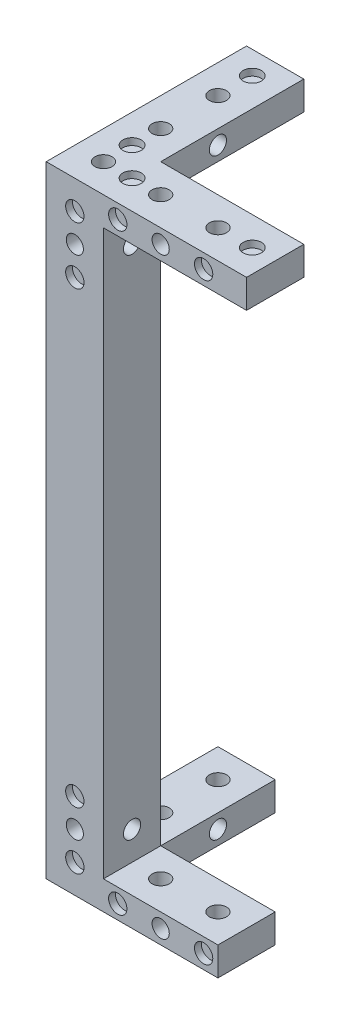
SolidWorks part; units mm, degrees
ref_plane "Front Plane" through (0, 0, 0) normal (0, 0, 1) x (1, 0, 0)
ref_plane "Top Plane" through (0, 0, 0) normal (0, 1, 0) x (1, 0, 0)
ref_plane "Right Plane" through (0, 0, 0) normal (1, 0, 0) x (0, 0, -1)
sketch "Sketch1" plane through (0, 0, 0) normal (0, 1, 0) x (1, 0, 0)
  line L1 (0, 0) -> (30, 0)
  line L2 (0, 0) -> (0, 10)
  line L3 (0, 10) -> (30, 10)
  line L4 (30, 0) -> (30, 10)
  line L5 (0, 0) -> (10, 0)
  line L6 (0, 0) -> (0, 30)
  line L7 (0, 30) -> (10, 30)
  line L8 (10, 0) -> (10, 30)
  dimension "D1" = 10
  dimension "D2" = 10
  dimension "D3" = 30
  dimension "D4" = 30
extrude "Boss-Extrude1" add sketch "Sketch1" along normal blind 10 contours L3 L8 L7 L6 | L1 L8 L3 L2 | L8 L1 L4 L3 region at (5, 0, -5) region at (20, 0, -5) region at (5, 0, -20)
sketch "Sketch2" plane through (0, 10, 0) normal (0, 1, 0) x (1, 0, 0)
  line L1 (0, 0) -> (10, 0)
  line L2 (0, 0) -> (0, 10)
  line L3 (0, 10) -> (10, 10)
  line L4 (10, 0) -> (10, 10)
extrude "Boss-Extrude2" add sketch "Sketch2" along normal blind 93.5
sketch "Sketch3" plane through (0, 103.5, 0) normal (0, 1, 0) x (1, 0, 0)
  line L1 (0, 0) -> (30, 0)
  line L2 (0, 0) -> (0, 10)
  line L3 (0, 10) -> (30, 10)
  line L4 (30, 0) -> (30, 10)
  line L5 (0, 0) -> (10, 0)
  line L6 (0, 0) -> (0, 30)
  line L7 (0, 30) -> (10, 30)
  line L8 (10, 0) -> (10, 30)
  line M9 (0, 10) -> (0, 0)
  line M10 (0, 0) -> (10, 0)
  line M11 (10, 0) -> (10, 10)
  line M12 (10, 10) -> (0, 10)
  dimension "D1" = 10
  dimension "D2" = 30
  dimension "D3" = 10
  dimension "D4" = 30
extrude "Boss-Extrude3" add sketch "Sketch3" along normal blind 5 contours L8 L7 L6 M12 | M12 M9 M10 M11 | L1 L4 L3 M11 region at (5, 103.5, -5) region at (20, 103.5, -5) region at (5, 103.5, -20)
sketch "Sketch4" plane through (0, 10, 0) normal (0, 1, 0) x (1, 0, 0)
  line L1 (30, 10) -> (10, 10)
  line L2 (30, 10) -> (30, 0)
  line L3 (30, 0) -> (10, 0)
  line L4 (10, 10) -> (10, 0)
  line L5 (10, 30) -> (0, 30)
  line L6 (10, 30) -> (10, 10)
  line L7 (10, 10) -> (0, 10)
  line L8 (0, 30) -> (0, 10)
  line M1 (10, 10) -> (10, 0)
  line M2 (10, 0) -> (30, 0)
  line M3 (30, 0) -> (30, 10)
  line M4 (30, 10) -> (10, 10)
extrude "Cut-Extrude1" cut sketch "Sketch4" against normal blind 5 contours L5 L8 L7 L6 | M4 M1 M2 M3 region at (20, 10, -5) region at (5, 10, -20)
sketch "Sketch5" plane through (0, 0, 0) normal (0, 0, 1) x (1, 0, 0)
  line L0 (10, 103.5) -> (10, 5) construction
  line L1 (0, 0) -> (30, 0) construction
  line L2 (10, 5) -> (30, 5) construction
  line L3 (30, 5) -> (30, 0) construction
  line L4 (0, 108.5) -> (0, 0) construction
  line L5 (0, 108.5) -> (0, 0)
  line L6 (0, 54.25) -> (10, 54.25)
  circle A0 centre (5, 5) radius 1.6
  circle A1 centre (27.5, 2.5) radius 1.6
  circle A2 centre (5, 15) radius 1.6
  circle A3 centre (12.5, 2.5) radius 1.6
  circle A4 centre (27.5, 106) radius 1.6
  circle A5 centre (12.5, 106) radius 1.6
  circle A6 centre (5, 103.5) radius 1.6
  circle A7 centre (5, 93.5) radius 1.6
  dimension "D1" = 3.2
  dimension "D2" = 5
  dimension "D3" = 5
  dimension "D4" = 3.2
  dimension "D5" = 2.5
  dimension "D6" = 2.5
  dimension "D7" = 2.5
  dimension "D8" = 3.2
  dimension "D9" = 5
  dimension "D10" = 10
  dimension "D11" = 3.2
  dimension "D12" = 15
extrude "Cut-Extrude2" cut sketch "Sketch5" against normal blind 1.2 contours A4 | A5 | A6 | A7 | A2 | A0 | A3 | A1
sketch "Sketch6" plane through (0, 0, 0) normal (0, 0, 1) x (1, 0, 0)
  line L0 (10, 103.5) -> (30, 103.5) construction
  line L1 (10, 103.5) -> (10, 5) construction
  line L2 (0, 108.5) -> (0, 0)
  line L3 (0, 54.25) -> (10, 54.25)
  circle A0 centre (5, 98.5) radius 1.5
  circle A1 centre (20, 106) radius 1.5
  circle A2 centre (5, 103.5) radius 1.6 construction
  circle A4 centre (20, 2.5) radius 1.5
  circle A5 centre (5, 10) radius 1.5
  circle A6 centre (27.5, 106) radius 1.6 construction
  circle A7 centre (12.5, 106) radius 1.6 construction
  dimension "D1" = 3
  dimension "D2" = 2.5
  dimension "D3" = 5
  dimension "D4" = 3
  dimension "D5" = 5
  dimension "D6" = 7.5
  dimension "D7" = 7.5
extrude "Cut-Extrude3" cut sketch "Sketch6" against normal blind 10 contours A1 | A0 | A5 | A4 region at (5, 98.5, 0) region at (20, 106, 0) region at (20, 2.5, 0) region at (5, 10, 0)
sketch "Sketch7" plane through (0, 0, 0) normal (-1, 0, 0) x (0, 0, 1)
  line L0 (0, 108.5) -> (-30, 108.5) construction
  line L1 (0, 108.5) -> (0, 0) construction
  line L5 (-30, 108.5) -> (-30, 103.5) construction
  line L8 (0, 108.5) -> (0, 0)
  line L9 (0, 54.25) -> (-10, 54.25)
  line L10 (-10, 103.5) -> (-10, 5) construction
  circle A0 centre (-27.5, 106) radius 1.6
  circle A1 centre (-12.5, 106) radius 1.6
  circle A2 centre (-5, 103.5) radius 1.6
  circle A3 centre (-5, 93.5) radius 1.6
  circle A4 centre (-5, 15) radius 1.6
  circle A5 centre (-5, 5) radius 1.6
  circle A6 centre (-12.5, 2.5) radius 1.6
  circle A7 centre (-27.5, 2.5) radius 1.6
  dimension "D1" = 3.2
  dimension "D2" = 3.2
  dimension "D3" = 3.2
  dimension "D4" = 3.2
  dimension "D5" = 2.5
  dimension "D6" = 2.5
  dimension "D7" = 5
  dimension "D8" = 5
  dimension "D9" = 2.5
  dimension "D10" = 15
  dimension "D11" = 5
  dimension "D12" = 10
extrude "Cut-Extrude4" cut sketch "Sketch7" against normal blind 1.2 contours A0 | A1 | A2 | A3 | A7 | A6 | A5 | A4 region at (0, 106, -27.5) region at (0, 106, -12.5) region at (0, 103.5, -5) region at (0, 93.5, -5) region at (0, 15, -5) region at (0, 5, -5) region at (0, 2.5, -12.5) region at (0, 2.5, -27.5)
sketch "Sketch8" plane through (0, 0, 0) normal (-1, 0, 0) x (0, 0, 1)
  line L0 (0, 108.5) -> (-30, 108.5) construction
  line L1 (0, 108.5) -> (0, 0) construction
  line L2 (-30, 108.5) -> (-30, 103.5) construction
  line L3 (0, 108.5) -> (0, 0)
  line L4 (0, 54.25) -> (-10, 54.25)
  line L5 (-10, 103.5) -> (-10, 5) construction
  circle A0 centre (-20, 106) radius 1.5
  circle A1 centre (-5, 98.5) radius 1.5
  circle A2 centre (-5, 103.5) radius 1.6 construction
  circle A3 centre (-5, 10) radius 1.5
  circle A4 centre (-20, 2.5) radius 1.5
  dimension "D1" = 3
  dimension "D2" = 3
  dimension "D3" = 2.5
  dimension "D4" = 5
  dimension "D5" = 5
  dimension "D6" = 10
extrude "Cut-Extrude5" cut sketch "Sketch8" against normal blind 10.2 contours A4 | A3 | A0 | A1
sketch "Sketch9" plane through (0, 5, 0) normal (0, 1, 0) x (1, 0, 0)
  circle A0 centre (25, 5) radius 1.5 construction
  circle A1 centre (15, 5) radius 1.5 construction
  circle A2 centre (25, 5) radius 1.5
  circle A3 centre (15, 5) radius 1.5
  circle A4 centre (5, 15) radius 1.5 construction
  circle A5 centre (5, 25) radius 1.5 construction
  circle A6 centre (5, 15) radius 1.5
  circle A7 centre (5, 25) radius 1.5
extrude "Cut-Extrude6" cut sketch "Sketch9" against normal blind 10.2
sketch "Sketch10" plane through (0, 0, 0) normal (0, -1, 0) x (1, 0, 0)
  circle A0 centre (5, -5) radius 1.5 construction
  circle A1 centre (5, -5) radius 1.5
extrude "Cut-Extrude7" cut sketch "Sketch10" against normal blind 12.2
sketch "Sketch11" plane through (0, 108.5, 0) normal (0, 1, 0) x (1, 0, 0)
  circle A0 centre (5, 15) radius 1.5 construction
  circle A1 centre (5, 25) radius 1.5 construction
  circle A2 centre (15, 5) radius 1.5 construction
  circle A3 centre (25, 5) radius 1.5 construction
  circle A4 centre (5, 15) radius 1.5
  circle A5 centre (5, 25) radius 1.5
  circle A6 centre (15, 5) radius 1.5
  circle A7 centre (25, 5) radius 1.5
extrude "Cut-Extrude8" cut sketch "Sketch11" against normal blind 10
sketch "Sketch12" plane through (0, 108.5, 0) normal (0, 1, 0) x (1, 0, 0)
  circle A0 centre (5, 5) radius 1.5 construction
  circle A1 centre (5, 5) radius 1.5
extrude "Cut-Extrude9" cut sketch "Sketch12" against normal blind 12
sketch "Sketch13" plane through (0, 108.5, 0) normal (0, 1, 0) x (1, 0, 0)
  line L1 (0, 0) -> (30, 0) construction
  line L2 (0, 0) -> (0, 30) construction
  circle A1 centre (10, 5) radius 1.6
  circle A2 centre (5, 10) radius 1.6
  circle A6 centre (5, 15) radius 1.5 construction
  circle A8 centre (15, 5) radius 1.5 construction
  dimension "D2" = 3.2
  dimension "D4" = 3.2
  dimension "D7" = 5
  dimension "D8" = 5
  dimension "D10" = 5
  dimension "D11" = 5
extrude "Cut-Extrude10" cut sketch "Sketch13" against normal blind 1.2
sketch "Sketch14" plane through (0, 0, -30) normal (0, 0, -1) x (-1, 0, 0)
  line L4 (-10, 103.5) -> (0, 103.5)
  line L5 (0, 103.5) -> (0, 108.5)
  line L6 (0, 108.5) -> (-10, 108.5)
  line L7 (-10, 108.5) -> (-10, 103.5)
  line L8 (-10, 103.5) -> (0, 103.5)
  line L9 (0, 103.5) -> (0, 108.5)
  line L10 (0, 108.5) -> (-10, 108.5)
  line L11 (-10, 108.5) -> (-10, 103.5)
  dimension "D1" = 0
extrude "Boss-Extrude4" add sketch "Sketch14" along normal blind 5
sketch "Sketch15" plane through (30, 0, 0) normal (1, 0, 0) x (0, 0, -1)
  line L4 (0, 103.5) -> (10, 103.5)
  line L5 (10, 103.5) -> (10, 108.5)
  line L6 (10, 108.5) -> (0, 108.5)
  line L7 (0, 108.5) -> (0, 103.5)
  line L8 (0, 103.5) -> (10, 103.5)
  line L9 (10, 103.5) -> (10, 108.5)
  line L10 (10, 108.5) -> (0, 108.5)
  line L11 (0, 108.5) -> (0, 103.5)
  dimension "D1" = 0
extrude "Boss-Extrude5" add sketch "Sketch15" along normal blind 5
sketch "Sketch16" plane through (0, 108.5, 0) normal (0, 1, 0) x (1, 0, 0)
  line L0 (0, 0) -> (35, 0) construction
  line L1 (0, 0) -> (0, 35) construction
  line L2 (35, 10) -> (35, 0) construction
  line L3 (0, 35) -> (10, 35) construction
  circle A0 centre (31, 5) radius 1.6
  circle A1 centre (5, 31) radius 1.6
  dimension "D1" = 3.2
  dimension "D2" = 3.2
  dimension "D3" = 5
  dimension "D4" = 5
  dimension "D5" = 4
  dimension "D6" = 4
extrude "Cut-Extrude11" cut sketch "Sketch16" against normal up to surface (1.2 mm away) up to face at (5, 107.3, -8.4)
